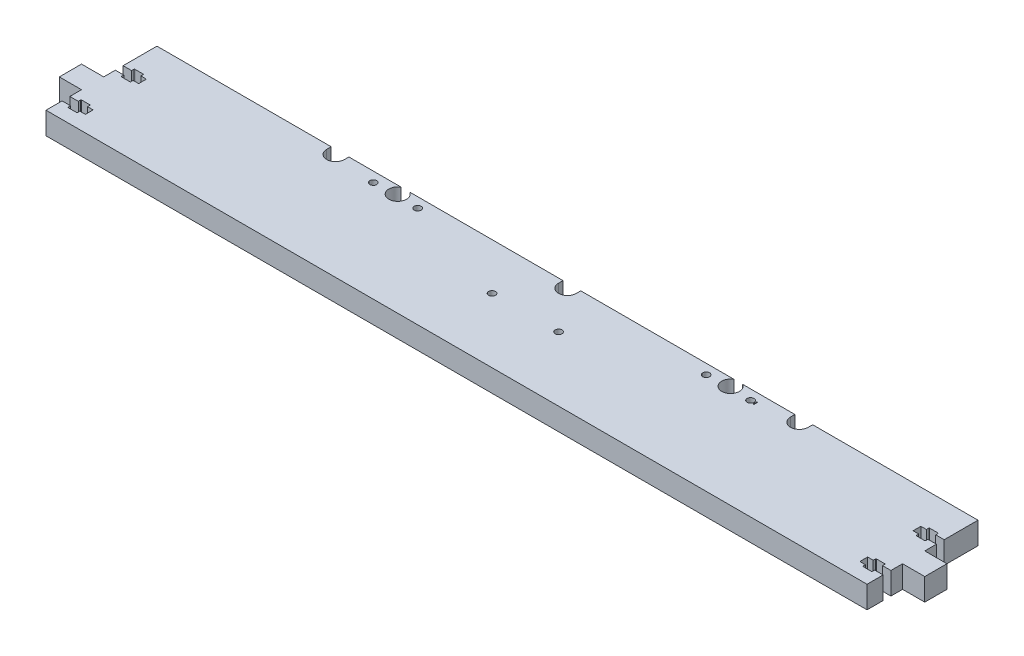
SolidWorks part; units mm, degrees
ref_plane "Front Plane" through (0, 0, 0) normal (0, 0, 1) x (1, 0, 0)
ref_plane "Top Plane" through (0, 0, 0) normal (0, 1, 0) x (1, 0, 0)
ref_plane "Right Plane" through (0, 0, 0) normal (1, 0, 0) x (0, 0, -1)
sketch "Sketch1" plane through (0, 0, 0) normal (0, 1, 0) x (1, 0, 0)
  line L0 (0, 25) -> (0, -25)
  line L1 (-185, 25) -> (0, 25)
  line L2 (-185, 25) -> (-185, -25) construction
  line L3 (-185, -25) -> (0, -25)
  line L4 (-185, -4) -> (-195, -4) construction
  line L5 (-185, 25) -> (0, 0) construction
  line L6 (-185, -25) -> (0, 0) construction
  line L7 (-185, -9) -> (-195, -9)
  line L8 (-195, -9) -> (-195, 1)
  line L9 (-195, 1) -> (-185, 1)
  line L10 (-185, 1) -> (-185, 25)
  line L11 (-185, -9) -> (-185, -25)
  line L47 (0, -25) -> (0, 25) construction
  line L89 (0, -25) -> (0, 25) construction
  point P0 (0, 0)
  dimension "D1" = 185
  dimension "D25" = 25
  dimension "D4" = 50
  dimension "D3" = 21
  dimension "D5" = 10
  dimension "D6" = 10
  dimension "D7" = 5
extrude "MainBody" add sketch "Sketch1" along normal blind 10 contours L3 region at (-93.5428, 0, 0.0428)
sketch "Sketch5" plane through (0, 10, 0) normal (0, 1, 0) x (1, 0, 0)
  line L0 (-185, 8) -> (-174.5, 8) construction
  line L1 (-185, 1) -> (-185, 25) construction
  line L2 (-185, 9.75) -> (-174.5, 9.75) construction
  line L3 (-174.5, 9.75) -> (-174.5, 6.25) construction
  line L4 (-174.5, 6.25) -> (-185, 6.25) construction
  line L5 (-185, 9.75) -> (-181.2, 9.75)
  line L6 (-181.2, 9.75) -> (-181.2, 10.75)
  line L7 (-180.95, 11) -> (-177.25, 11)
  line L8 (-177, 10.75) -> (-177, 9.75)
  line L9 (-177, 9.75) -> (-174.5, 9.75)
  line L10 (-174.5, 9.75) -> (-174.5, 6.25)
  line L11 (-185, 6.25) -> (-185, 9.75)
  line L12 (-195, -9) -> (-195, 1) construction
  line L13 (-185, 6.25) -> (-174.5, 6.25) construction
  line L14 (-177, 6.25) -> (-174.5, 6.25)
  line L15 (-177, 5.25) -> (-177, 6.25)
  line L16 (-180.95, 5) -> (-177.25, 5)
  line L17 (-181.2, 6.25) -> (-181.2, 5.25)
  line L18 (-185, 6.25) -> (-181.2, 6.25)
  line L19 (-185, 1) -> (-185, -9) construction
  line L20 (-195, -4) -> (-185, -4) construction
  line L21 (-195, -9) -> (-195, 1) construction
  line L22 (-185, -14.25) -> (-174.5, -14.25) construction
  line L23 (-174.5, -14.25) -> (-185, -14.25) construction
  line L24 (-174.5, -17.75) -> (-174.5, -14.25) construction
  line L25 (-185, -17.75) -> (-174.5, -17.75) construction
  line L26 (-185, -16) -> (-174.5, -16) construction
  line L27 (-185, -14.25) -> (-181.2, -14.25)
  line L28 (-181.2, -14.25) -> (-181.2, -13.25)
  line L29 (-180.95, -13) -> (-177.25, -13)
  line L30 (-177, -13.25) -> (-177, -14.25)
  line L31 (-177, -14.25) -> (-174.5, -14.25)
  line L32 (-185, -14.25) -> (-185, -17.75)
  line L33 (-174.5, -17.75) -> (-174.5, -14.25)
  line L34 (-177, -17.75) -> (-174.5, -17.75)
  line L35 (-177, -18.75) -> (-177, -17.75)
  line L36 (-180.95, -19) -> (-177.25, -19)
  line L37 (-181.2, -17.75) -> (-181.2, -18.75)
  line L38 (-185, -17.75) -> (-181.2, -17.75)
  line L39 (-185, 6.25) -> (-174.5, 6.25) construction
  arc A0 (-177.25, 11) -> (-177, 10.75) centre (-177.25, 10.75) cw
  arc A1 (-181.2, 10.75) -> (-180.95, 11) centre (-180.95, 10.75) cw
  arc A2 (-181.2, 5.25) -> (-180.95, 5) centre (-180.95, 5.25) ccw
  arc A3 (-177.25, 5) -> (-177, 5.25) centre (-177.25, 5.25) ccw
  arc A4 (-177.25, -13) -> (-177, -13.25) centre (-177.25, -13.25) cw
  arc A5 (-181.2, -13.25) -> (-180.95, -13) centre (-180.95, -13.25) cw
  arc A6 (-181.2, -18.75) -> (-180.95, -19) centre (-180.95, -18.75) ccw
  arc A7 (-177.25, -19) -> (-177, -18.75) centre (-177.25, -18.75) ccw
  point P6 (-195, -4)
  point P17 (-177, 11)
  point P20 (-181.2, 11)
  point P29 (-181.2, 5)
  point P30 (-177, 5)
  point P61 (-177, -13)
  point P62 (-181.2, -13)
  point P63 (-181.2, -19)
  point P64 (-177, -19)
  dimension "D8" = 0.25
  dimension "D1" = 10.5
  dimension "D2" = 1.75
  dimension "D4" = 4.2
  dimension "D5" = 8
  dimension "D6" = 3
  dimension "D7" = 12
extrude "ScrewCutouts" cut sketch "Sketch5" against normal through all
mirror "Mirror1" about plane through (0, 0, 0) normal (1, 0, 0) of "ScrewCutouts", "MainBody"
sketch "Sketch3" plane through (0, 10, 0) normal (0, 1, 0) x (1, 0, 0)
  line L0 (2, 25) -> (2, -25) construction
  line L1 (-185, 25) -> (185, 25) construction
  line L2 (-185, -25) -> (185, -25) construction
  line L3 (-63, 20.5) -> (-83, 20.5) construction
  line L4 (-73, 17.5) -> (-73, 25.5) construction
  line L5 (77, 17.5) -> (77, 25.5) construction
  line L6 (67, 20.5) -> (87, 20.5) construction
  circle A0 centre (-73, 21.5) radius 4
  circle A1 centre (-83, 20.5) radius 1.55
  circle A2 centre (-63, 20.5) radius 1.55
  circle A3 centre (67, 20.5) radius 1.55
  circle A4 centre (87, 20.5) radius 1.55
  circle A5 centre (77, 21.5) radius 4
  dimension "D2" = 8
  dimension "D4" = 3.1
  dimension "D1" = 3.5
  dimension "D5" = 75
  dimension "D6" = 2
  dimension "D3" = 10
  dimension "D7" = 1
extrude "RodCutouts" cut sketch "Sketch3" against normal through all
sketch "Sketch6" plane through (0, 10, 0) normal (0, 1, 0) x (1, 0, 0)
  line L0 (-73, 21.5) -> (77, 21.5) construction
  line L1 (2, 21.5) -> (2, -25) construction
  line L2 (-185, -25) -> (185, -25) construction
  line L3 (17, 4) -> (-13, 4) construction
  line L4 (-71.0635, 25) -> (75.0635, 25) construction
  circle A0 centre (-13, 4) radius 1.55
  circle A1 centre (17, 4) radius 1.55
  point P13 (2, 4)
  dimension "D3" = 21
  dimension "D1" = 3.1
  dimension "D2" = 15
extrude "Cut-Extrude1" cut sketch "Sketch6" against normal through all
sketch "Sketch7" plane through (0, 10, 0) normal (0, 1, 0) x (1, 0, 0)
  line L0 (-73, 21.5) -> (77, 21.5) construction
  line L1 (2, 21.5) -> (2, -25) construction
  line L3 (-102.5, 25) -> (-102.5, 23) construction
  line L4 (-185, 25) -> (-74.9365, 25) construction
  line L5 (-98.5, 25) -> (-98.5, 23)
  line L6 (-106.5, 25) -> (-106.5, 23)
  line L7 (106.5, 25) -> (106.5, 23) construction
  line L8 (102.5, 25) -> (102.5, 23)
  line L9 (110.5, 25) -> (110.5, 23)
  line L12 (-185, -25) -> (185, -25) construction
  arc A0 (-98.5, 25) -> (-106.5, 25) centre (-102.5, 25) ccw
  arc A1 (-106.5, 23) -> (-98.5, 23) centre (-102.5, 23) ccw
  arc A2 (102.5, 25) -> (110.5, 25) centre (106.5, 25) cw
  arc A3 (110.5, 23) -> (102.5, 23) centre (106.5, 23) cw
  point P12 (-102.5, 24)
  point P19 (106.5, 24)
  dimension "D1" = 4
  dimension "D2" = 2
  dimension "D3" = 104.5
extrude "BedAdjustmentScrewCutout" cut sketch "Sketch7" against normal through all
sketch "Sketch8" plane through (0, 10, 0) normal (0, 1, 0) x (1, 0, 0)
  line L0 (88.35, 20.5) -> (89.35, 20.5) construction
  line L1 (88.55, 20.5) -> (88.55, 25) construction
  line L2 (88.35, 20.5) -> (89.35, 21.5)
  line L3 (89.35, 21.5) -> (89.35, 19.5)
  line L4 (88.35, 20.5) -> (89.35, 19.5)
  line L5 (78.9365, 25) -> (102.5, 25) construction
  circle A1 centre (87, 20.5) radius 1.55 construction
  point P9 (89.35, 20.5)
  dimension "D1" = 1
  dimension "D2" = 1
  dimension "D3" = 0.2
extrude "DirectionKey" cut sketch "Sketch8" against normal through all
sketch "Sketch9" plane through (0, 10, 0) normal (0, 1, 0) x (1, 0, 0)
  line L0 (-13, 4) -> (17, 4) construction
  line L1 (2, 4) -> (2, 25) construction
  line L2 (-71.0635, 25) -> (75.0635, 25) construction
  line L3 (2, 27) -> (2, 23) construction
  line L4 (6, 27) -> (6, 23)
  line L5 (-2, 27) -> (-2, 23)
  arc A0 (6, 27) -> (-2, 27) centre (2, 27) ccw
  arc A1 (-2, 23) -> (6, 23) centre (2, 23) ccw
  point P10 (2, 25)
  dimension "D1" = 4
  dimension "D2" = 2
extrude "Cut-Extrude2" cut sketch "Sketch9" against normal through all
equation "\"Y-ROD-SPACING\"=75"
equation "\"Y-BED-OFFSET\"=2"
equation "\"T-SLOT-NUT-FILLET-RADIUS\"=0.25"
equation "\"T-SLOT-SCREW-SHAFT-RADIUS\"=1.75"
equation "\"T-SLOT-SCREW-SHAFT-CUTOUT-LENGTH\"=10.5"
equation "\"T-SLOT-NUT-DEPTH\"=4.2"
equation "\"T-SLOT-NUT-WIDTH\"=3"
equation "\"T-SLOT-NUT-END-DISTANCE\"=8"
equation "\"ACRYLIC-TAB-CUTOUT-SIZE\"=\"ACRYLIC-THICKNESS\"+\"ACRYLIC-TAB-TOLERANCE\"*2"
equation "\"ACRYLIC-M3-HOLE\"=3.1"
equation "\"D1@Sketch5\"=\"T-SLOT-SCREW-SHAFT-CUTOUT-LENGTH\""
equation "\"D2@Sketch5\"=\"T-SLOT-SCREW-SHAFT-RADIUS\""
equation "\"D4@Sketch5\"=\"T-SLOT-NUT-DEPTH\""
equation "\"D5@Sketch5\"=\"T-SLOT-NUT-END-DISTANCE\""
equation "\"D6@Sketch5\"=\"T-SLOT-NUT-WIDTH\""
equation "\"D8@Sketch5\"=\"T-SLOT-NUT-FILLET-RADIUS\""
equation "\"D4@Sketch3\"=\"ACRYLIC-M3-HOLE\""
equation "\"D5@Sketch3\"=\"Y-ROD-SPACING\""
equation "\"D6@Sketch3\"=\"Y-BED-OFFSET\""
equation "\"Y-BED-ROD-INSET\"=3.5"
equation "\"D1@Sketch3\"=\"Y-BED-ROD-INSET\""
equation "\"SMOOTHROD-CAP-SCREW-DISTANCE\"=20"
equation "\"D3@Sketch3\"=\"SMOOTHROD-CAP-SCREW-DISTANCE\"/2"
equation "\"ACRYLIC-TAB-WIDTH\"=\"ACRYLIC-THICKNESS\""
equation "\"FRAME-WIDTH-INNER\"=370"
equation "\"D6@Sketch1\"=\"ACRYLIC-TAB-WIDTH\""
equation "\"D5@Sketch1\"=\"ACRYLIC-TAB-WIDTH\""
equation "\"D1@Sketch1\"=\"FRAME-WIDTH-INNER\"/2"
equation "\"X-ROD-SPACING\"=45"
equation "\"Z-ROD-SPACING\"=17.5"
equation "\"ACRYLIC-THICKNESS\"=10"
equation "\"ACRYLIC-THICKNESS2\"=4.5"
equation "\"NEMA17-HOLE-SPACING\"=31"
equation "\"NEMA17-CENTRAL-CUTOUT\"=22.5"
equation "\"Z-BRACKET-REACH\"=55"
equation "\"TOP-BRACKET-SPACING\"=40"
equation "\"SMOOTHROD-X-LENGTH\"=350"
equation "\"SMOOTHROD-Y-LENGTH\"=350"
equation "\"SMOOTHROD-Z-LENGTH\"=350"
equation "\"SMOOTHROD-TIGHTENING-HEADROOM\"=.25"
equation "\"LEADSCREW-Z-LENGTH\"=300"
equation "\"SCREW-LENGTH-FRAME\"=\"ACRYLIC-THICKNESS\" + 10"
equation "\"SCREW-HEAD-RADIUS\"=6"
equation "\"PRINTED-X-SMOOTHROD-DIAMETER\"=8.2"
equation "\"PRINTED-X-SMOOTHROD-CUTOUT\"=10"
equation "\"PRINTED-X-BASE-HEIGHT\"=10"
equation "\"PRINTED-LM8UU-CUTOUT-SIZE\"=15.25"
equation "\"PRINTED-LM8UU-CUTOUT-LENGTH\"=24.5"
equation "\"PRINTED-X-IDLER-HEIGHT\"=16"
equation "\"PSU-MOUNTING-WIDTH\"=95"
equation "\"PSU-MOUNTING-HEIGHT\"=177"
equation "\"D1@MainBody\"=\"ACRYLIC-THICKNESS\""
equation "\"D7@Sketch1\"=\"ACRYLIC-TAB-WIDTH\"/2"
equation "\"D1@Sketch6\"=\"ACRYLIC-M3-HOLE\""
equation "\"Y-BELT-TO-ROD-DISTANCE\"=20"
equation "\"Y-BED-SCREW-SPACING\"=209"
equation "\"Z-ROD-INSET\"=16"
equation "\"SPOOL-HOLDER-ROD-SPACING\"=150"
equation "\"D3@Sketch7\"=\"Y-BED-SCREW-SPACING\"/2"
equation "\"Y-BED-SCREW-CUTOUT-SLOT-HEIGHT\"=2"
equation "\"D2@Sketch7\"=\"Y-BED-SCREW-CUTOUT-SLOT-HEIGHT\""
equation "\"ACRYLIC-TAB-TOLERANCE\"=.1"
equation "\"SCREW-LENGTH-MOTOR\"=\"ACRYLIC-THICKNESS\" + 5"
equation "\"SCREW-LENGTH-EXTRUDER\"=28"
equation "\"PRINTED-M3-HOLE\"=3.5"
equation "\"ACRYLIC-X-CARRIAGE-WIDTH\"=55"
equation "\"ACRYLIC-X-CARRIAGE-HEIGHT\"=75"
equation "\"ACRYLIC-X-CARRIAGE-LM8UU-CUTOUT-WIDTH\"=24.25"
equation "\"ACRYLIC-X-CARRIAGE-LM8UU-CUTOUT-HEIGHT\"=11.5"
equation "\"ACRYLIC-X-CARRIAGE-SCREW-SPACING-X\"=15"
equation "\"ACRYLIC-X-CARRIAGE-SCREW-SPACING-Y\"=33"
equation "\"ACRYLIC-X-CARRIAGE-CENTER-TAB-SPACING\"=14"
equation "\"ACRYLIC-X-CARRIAGE-EXTRUDER-OFFSET\"=26"
equation "\"ACRYLIC-X-CARRIAGE-EXTRUDER-ANGLE\"=90"
equation "\"ACRYLIC-X-CARRIAGE-EXTRUDER-SHELF-DEPTH\"=\"ACRYLIC-X-CARRIAGE-EXTRUDER-OFFSET\" + 28"
equation "\"ACRYLIC-X-CARRIAGE-EXTRUDER-BRACE-SPACING\"=23"
equation "\"ACRYLIC-X-CARRIAGE-EXTRUDER-BRACE-TAB-OFFSET\"=20"
equation "\"ACRYLIC-X-CARRIAGE-EXTRUDER-BRACE-HEIGHT\"=35"
equation "\"ACRYLIC-X-CARRIAGE-EXTRUDER-BRACE-SCREW-SPACING\"=22"
equation "\"ACRYLIC-X-CARRIAGE-DUAL-WIDTH-MULTIPLIER\"=1.65"
equation "\"ACRYLIC-X-CARRIAGE-DUAL-HOTEND-SPACING\"=42"
equation "\"ACRYLIC-X-CARRIAGE-DUAL-WIDTH\"=75"
equation "\"ACRYLIC-X-CARRIAGE-DUAL-HOTEND-SEPARATION\"=36"
equation "\"ACRYLIC-X-CARRIAGE-DUAL-MOUNT-PLATE-DEPTH\"=75"
equation "\"ACRYLIC-X-CARRIAGE-DUAL-MOUNT-BRACE-WIDTH\"=33"
equation "\"ACRYLIC-X-CARRIAGE-DUAL-MOUNT-SCREW-WIDTH\"=40"
equation "\"BLOWER-FAN-WIDTH\"=15"
equation "\"D2@Sketch9\"=\"Y-BED-SCREW-CUTOUT-SLOT-HEIGHT\""
